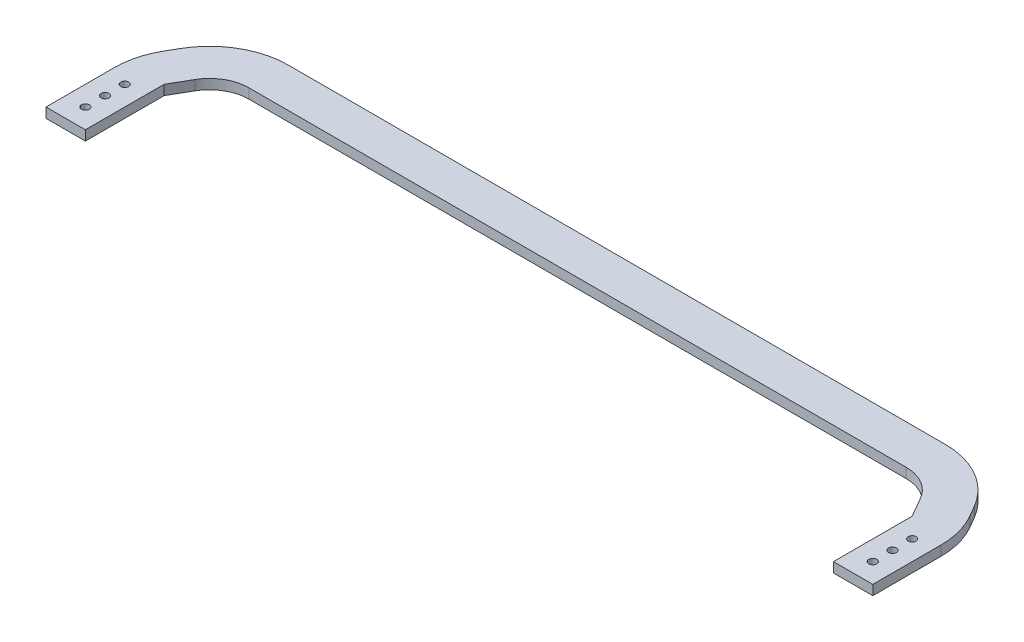
SolidWorks part; units mm, degrees
material "6061-T6 (SS)"
ref_plane "Front" through (0, 0, 0) normal (0, 0, 1) x (1, 0, 0)
ref_plane "Top" through (0, 0, 0) normal (0, 1, 0) x (1, 0, 0)
ref_plane "Right" through (0, 0, 0) normal (1, 0, 0) x (0, 0, -1)
sketch "Sketch1" plane through (0, 0, 0) normal (0, 1, 0) x (1, 0, 0)
  line L0 (-241.3, -50.8) -> (-241.3, 0)
  line L1 (241.3, 0) -> (241.3, -50.8)
  line L2 (241.3, -50.8) -> (266.7, -50.8)
  line L3 (0, 0) -> (0, -66.2098) construction
  line L4 (-241.3, -50.8) -> (-266.7, -50.8)
  line L5 (-266.7, -50.8) -> (-266.7, -6.8059)
  line L6 (266.7, -6.8059) -> (266.7, -50.8)
  line L7 (-241.3, 0) -> (-233.9677, 12.7)
  line L8 (-211.9706, 25.4) -> (211.9706, 25.4)
  line L9 (-241.3, 0) -> (241.3, 0) construction
  line L10 (233.9677, 12.7) -> (241.3, 0)
  line L11 (259.8941, 18.5941) -> (255.9647, 25.4)
  line L12 (211.9706, 50.8) -> (-211.9706, 50.8)
  line L13 (-255.9647, 25.4) -> (-259.8941, 18.5941)
  line L14 (266.7, 6.8059) -> (266.7, -50.8) construction
  line L15 (-266.7, -50.8) -> (-266.7, 6.8059) construction
  arc A6 (225.428, 9.9217) -> (241.3, 0) centre (220.8476, -15.0619) cw construction
  arc A7 (-266.7, 6.8059) -> (-233.3972, 51.5572) centre (-82.6041, -95.4263) cw construction
  arc A8 (-233.3972, 51.5572) -> (230.0083, 34.9053) centre (-58.5524, -1539.0619) cw construction
  arc A9 (230.0083, 34.9053) -> (266.7, 6.8059) centre (220.8476, -15.0619) cw construction
  arc A10 (-241.3, 0) -> (-221.2635, 27.3097) centre (-82.6041, -95.4263) cw construction
  arc A11 (-221.2635, 27.3097) -> (225.428, 9.9217) centre (-58.5524, -1539.0619) cw construction
  arc A12 (259.8941, 18.5941) -> (266.7, -6.8059) centre (215.9, -6.8059) cw
  arc A13 (255.9647, 25.4) -> (211.9706, 50.8) centre (211.9706, 0) ccw
  arc A14 (-266.7, -6.8059) -> (-259.8941, 18.5941) centre (-215.9, -6.8059) cw
  arc A15 (-211.9706, 50.8) -> (-255.9647, 25.4) centre (-211.9706, 0) ccw
  arc A16 (211.9706, 25.4) -> (233.9677, 12.7) centre (211.9706, 0) cw
  arc A17 (-233.9677, 12.7) -> (-211.9706, 25.4) centre (-211.9706, 0) cw
  dimension "D4" = 30
  dimension "D8" = 50.8
  dimension "D9" = 25.4
  dimension "D1" = 482.6
  dimension "D2" = 50.8
  dimension "D5" = 25.4
  dimension "D6" = 25.4
  dimension "D7" = 25.4
  dimension "D3" = 25.4
extrude "Boss-Extrude1" add sketch "Sketch1" along normal blind 6.35
hole_wizard "#10 Clearance Hole1" positions "Sketch2" profile "Sketch3" hole size "#10" standard "ANSI Inch" end condition through all
sketch "Sketch2" plane through (0, 6.35, 0) normal (0, 1, 0) x (1, 0, 0)
  line L3 (-266.7, -50.8) -> (-254, -38.1) construction
  line L4 (-254, -38.1) -> (-254, -25.4) construction
  line L5 (-254, -25.4) -> (-254, -12.7) construction
  line L6 (-254, -12.7) -> (-241.3, 0) construction
  line L8 (0, 0) -> (0, -50.8) construction
  point P0 (-254, -38.1)
  point P2 (-254, -25.4)
  point P4 (-254, -12.7)
  point P29 (254, -12.7)
  point P30 (254, -25.4)
  point P31 (254, -38.1)
  dimension "D1" = 12.7
sketch "Sketch3" plane through (-254, 6.35, 38.1) normal (1, 0, 0) x (0, 0, 1)
  line L0 (0, 0) -> (0, 6.35)
  line L1 (0, 6.35) -> (2.5527, 6.35)
  line L2 (2.5527, 6.35) -> (2.5527, 0)
  line L5 (2.5527, 0) -> (0, 0)
  line L11 (0, -6.35) -> (0, 107.95) construction
  dimension "Thru Hole Dia." = 5.1054
  dimension "Thru Hole Depth" = 6.35
